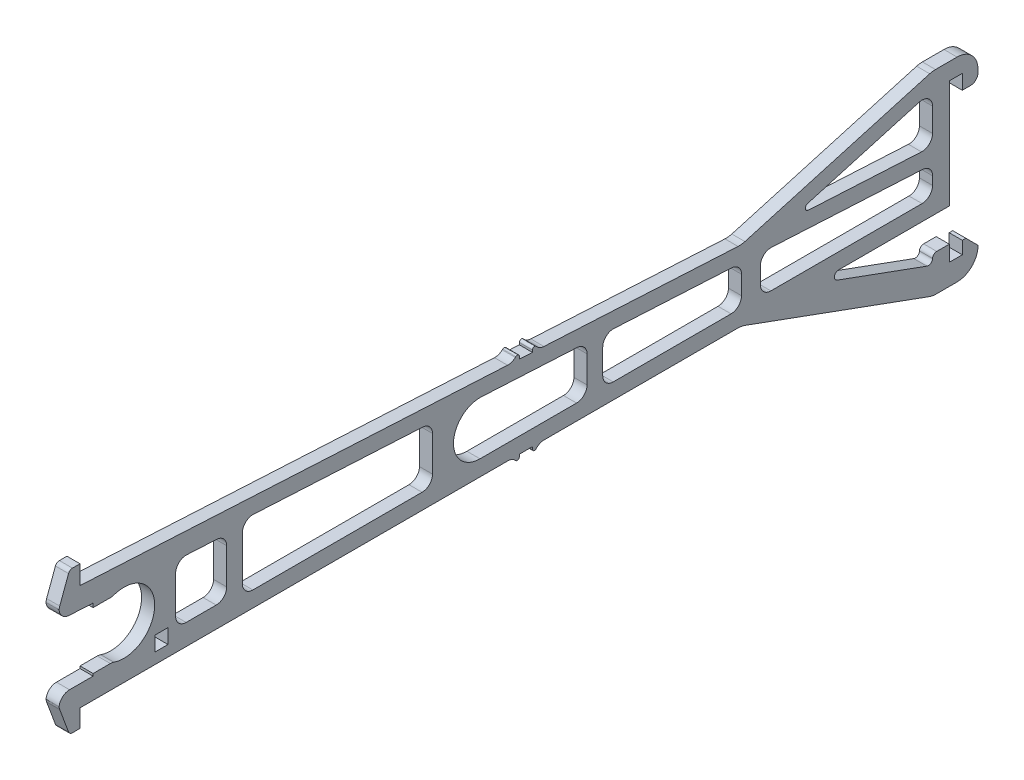
SolidWorks part; units mm, degrees
material "Delrin"
ref_plane "Front Plane" through (0, 0, 0) normal (0, 0, 1) x (1, 0, 0)
ref_plane "Top Plane" through (0, 0, 0) normal (0, 1, 0) x (1, 0, 0)
ref_plane "Right Plane" through (0, 0, 0) normal (1, 0, 0) x (0, 0, -1)
sketch "Sketch1" plane through (0, 0, 0) normal (1, 0, 0) x (0, 0, -1)
  line L0 (0.3361, 6.2648) -> (74.8851, 2.2655)
  line L1 (0, -6.2738) -> (74.8851, -6.2738)
  line L2 (98.044, 8.8972) -> (101.0158, 8.8972)
  line L3 (12.4587, 3.0708) -> (0.2, 3.7284)
  line L4 (12.4587, -3.7338) -> (0, -3.7338)
  line L5 (-5.3213, -3.7338) -> (-7.8613, -3.7338)
  line L6 (52.6413, 3.4588) -> (52.6413, 1.5538) construction
  line L7 (98.044, -6.2738) -> (98.044, 8.8972) construction
  line L8 (-5.3213, 0.003) -> (-5.3213, 22.0412) construction
  line L9 (0.3361, 6.2648) -> (-5.3213, 6.5683)
  line L10 (-5.3213, 6.5683) -> (-5.3213, 8.8599)
  line L11 (-5.3213, 8.8599) -> (-7.8613, 8.8599)
  line L12 (-7.8613, 8.8599) -> (-7.8613, 4.1609)
  line L13 (14.3637, 3.6073) -> (14.3637, 5.5123) construction
  line L14 (0, -6.2738) -> (-5.3213, -6.2738)
  line L15 (-5.3213, -6.2738) -> (-5.3213, -8.4328)
  line L16 (14.3637, 3.6073) -> (14.3637, -4.3688)
  line L17 (39.3251, 2.2682) -> (39.3251, -4.3688)
  line L18 (37.4201, 2.3704) -> (37.4201, -4.3688)
  line L19 (-5.3213, -8.4328) -> (-7.8613, -8.4328)
  line L20 (-7.8613, -8.4328) -> (-7.8613, -3.7338)
  line L21 (52.6413, -4.3688) -> (52.6413, -6.2738) construction
  line L22 (12.4587, 3.0708) -> (12.4587, -3.7338)
  line L23 (0, 3.7338) -> (0, -3.7338)
  line L24 (102.6668, 5.0872) -> (101.6508, 5.0872)
  line L25 (101.6508, 5.0872) -> (101.6508, 6.8652)
  line L26 (101.6508, 6.8652) -> (100.076, 6.8652)
  line L27 (100.076, 6.8652) -> (100.076, -6.2738)
  line L28 (100.076, -12.1848) -> (101.6508, -12.1848)
  line L29 (101.6508, -12.1848) -> (101.6508, -10.6608)
  line L30 (101.6508, -10.6608) -> (102.0826, -10.6608)
  line L31 (103.5558, -12.134) -> (103.5558, -12.1848)
  line L32 (101.0158, -14.7248) -> (98.044, -14.7248)
  line L33 (98.044, -14.7248) -> (98.044, -6.2738) construction
  line L34 (103.5558, 5.9762) -> (103.5558, 6.3572)
  line L35 (102.0826, -10.6608) -> (103.5558, -12.134)
  line L36 (77.1711, 0.2379) -> (77.1711, -4.3688)
  line L37 (74.8851, 0.3605) -> (74.8851, -4.3688)
  line L38 (74.8851, 2.2655) -> (98.044, 8.8972)
  line L39 (80.7132, 1.9529) -> (98.044, 6.9156)
  line L40 (74.8851, -6.2738) -> (98.044, -14.7248)
  line L41 (83.7765, -6.2738) -> (98.044, -11.4802)
  line L42 (75.93, -3.4105) -> (99.0889, -11.8615) construction
  line L43 (75.4095, 0.4341) -> (98.5684, 7.0658) construction
  line L44 (83.7765, -6.2738) -> (98.044, -6.2738)
  line L45 (-1.4111, 3.4569) -> (-3.7338, 3.4569)
  line L46 (80.7132, 1.9529) -> (98.044, 1.0232)
  line L47 (74.8851, -4.3678) -> (74.8851, 49995.6322) construction
  line L48 (98.044, 6.9156) -> (98.044, 1.0232)
  line L49 (98.044, -0.8818) -> (98.044, -4.3688)
  line L50 (100.076, -12.1848) -> (100.076, -10.2798)
  line L51 (98.044, -6.2738) -> (100.076, -6.2738)
  line L52 (100.076, -10.2798) -> (98.044, -10.2798)
  line L53 (98.044, -10.2798) -> (98.044, -11.4802)
  line L54 (14.3637, 3.6073) -> (37.4201, 2.3704)
  line L55 (14.3637, -4.3688) -> (37.4201, -4.3688)
  line L56 (39.3251, -4.3688) -> (74.8851, -4.3688)
  line L57 (39.3251, 2.2682) -> (74.8851, 0.3605)
  line L58 (77.1711, 0.2379) -> (98.044, -0.8818)
  line L59 (77.1711, -4.3688) -> (98.044, -4.3688)
  line L60 (-3.7338, 0) -> (-3.7338, 18.3871) construction
  line L61 (-3.7338, 3.9395) -> (-7.8613, 4.1609)
  line L62 (-3.7338, -3.7338) -> (-5.3213, -3.7338)
  line L63 (-3.7338, 3.4569) -> (-3.7338, 3.9395)
  line L64 (-1.4111, -3.4569) -> (-3.7338, -3.4569)
  line L65 (-3.7338, -3.4569) -> (-3.7338, -3.7338)
  line L66 (6.2738, 3.4026) -> (6.2738, -3.7338)
  line L67 (3.7338, 0) -> (3.7338, 11.926) construction
  line L68 (58.0576, 1.2633) -> (58.0576, -4.3688)
  line L69 (56.1526, 1.3655) -> (56.1526, -4.3688)
  line L70 (57.1051, -4.3688) -> (57.1051, 1.3144) construction
  line L71 (57.1051, -0.6088) -> (56.1526, -0.6088) construction
  line L72 (57.1051, -0.6088) -> (58.0576, -0.6088) construction
  arc A0 (0, -3.7338) -> (0, 3.7338) centre (0, 0) ccw
  circle A1 centre (0, 0) radius 6.2738 construction
  arc A2 (101.0158, 8.8972) -> (103.5558, 6.3572) centre (101.0158, 6.3572) cw
  arc A3 (103.5558, -12.1848) -> (101.0158, -14.7248) centre (101.0158, -12.1848) cw
  arc A4 (103.5558, 5.9762) -> (102.6668, 5.0872) centre (102.6668, 5.9762) cw
  arc A5 (0, 3.7338) -> (-1.4111, 3.4569) centre (0, 0) ccw
  circle A6 centre (0, 0) radius 3.7338 construction
  arc A7 (-1.4111, -3.4569) -> (0, -3.7338) centre (0, 0) ccw
  point P47 (103.5558, 8.8972)
  point P50 (103.5558, -14.7248)
  point P53 (103.5558, 5.0872)
  point P54 (103.5558, -10.6608)
  point P56 (103.5558, -10.6608)
  point P79 (3.5707, 1.0917)
  dimension "D1" = 7.4676
  dimension "D2" = 2.54
  dimension "D3" = 5.842
  dimension "D8" = 1.5748
  dimension "D18" = 2.54
  dimension "D19" = 2.54
  dimension "D20" = 0.889
  dimension "D21" = 35.56
  dimension "D5" = 37.4201
  dimension "D10" = 1.905
  dimension "D11" = 1.778
  dimension "D12" = 1.905
  dimension "D4" = 5.3842
  dimension "D9" = 1.5748
  dimension "D14" = 1.524
  dimension "D15" = 3.81
  dimension "D16" = 4.064
  dimension "D17" = 1.905
  dimension "D22" = 19.05
  dimension "D23" = 20.8729
  dimension "D24" = 2.032
  dimension "D25" = 2.286
  dimension "D29" = 1.905
  dimension "D13" = 2.54
  dimension "D30" = 4.699
  dimension "D31" = 1.905
  dimension "D32" = 17.78
  dimension "D33" = 1.5875
  dimension "D6" = 1.905
  dimension "D7" = 0.4826
  dimension "D34" = 2.54
  dimension "D35" = 1.905
  dimension "D27" = 3.048
  dimension "D28" = 1.905
extrude "Boss-Extrude1" add sketch "Sketch1" along normal blind 1.5875 contours A1 A0 | A4 L34 A2 L2 L38 L0 L9 L10 L11 L12 L49 L20 L19 L15 L14 L1 L40 L32 A3 L31 L35 L30 L29 L28 L50 L52 L53 L41 L44 L51 L27 L26 L25 L24 | L18 L17 | L22 L16 | L37 L36 | L57 L69 L56 L68 region at (0, 3.1279, -37.5496) region at (0, -0.1548, -4.5114) region at (0, -1.5271, -57.1022)
sketch "Sketch7" plane through (0, 0, 0) normal (-1, 0, 0) x (0, 0, 1)
  line L0 (6.5913, 8.8599) -> (7.8613, 5.4309)
  line L1 (5.3213, 8.8599) -> (7.8613, 8.8599) construction
  line L2 (7.8613, 8.8599) -> (7.8613, 4.1609) construction
  line L3 (6.5913, 8.8599) -> (7.8613, 8.8599)
  line L4 (7.8613, 8.8599) -> (7.8613, 5.4309)
  line L5 (6.5913, -8.4328) -> (7.8613, -5.0038)
  line L6 (5.3213, -8.4328) -> (7.8613, -8.4328) construction
  line L7 (7.8613, -8.4328) -> (7.8613, -3.7338) construction
  line L8 (6.5913, -8.4328) -> (7.8613, -8.4328)
  line L9 (7.8613, -8.4328) -> (7.8613, -5.0038)
  dimension "D1" = 1.27
  dimension "D2" = 1.27
  dimension "D3" = 1.27
extrude "Cut-Extrude2" cut sketch "Sketch7" against normal through all
fillet "Fillet1" radius 2.54 4 edges at (0.7937, 2.2655, -74.8851) (0.7937, 8.8972, -98.044) (0.7937, -6.2738, -74.8851) (0.7937, -14.7248, -98.044)
fillet "Fillet2" radius 1.27 20 edges at (0.7937, 1.0232, -98.044) (0.7937, 6.9156, -98.044) (0.7937, -4.3688, -14.3637) (0.7937, 3.6073, -14.3637) (0.7937, 2.3704, -37.4201) (0.7937, -4.3688, -37.4201) (0.7937, -4.3688, -77.1711) (0.7937, 0.2379, -77.1711) (0.7937, -4.3688, -98.044) (0.7937, -0.8818, -98.044) (0.7937, -4.3688, -74.8851) (0.7937, 0.3605, -74.8851) (0.7937, -3.7338, -6.2738) (0.7937, 3.4026, -6.2738) (0.7937, -3.7338, -12.4587) (0.7937, 3.0708, -12.4587) (0.7937, 1.3655, -56.1526) (0.7937, -4.3688, -56.1526) (0.7937, -4.3688, -58.0576) (0.7937, 1.2633, -58.0576)
fillet "Fillet3" radius 0.508 2 edges at (0.7937, -6.2738, -83.7765) (0.7937, -11.4802, -98.044)
fillet "Fillet4" radius 0.508 1 edges at (0.7937, -10.2798, -98.044)
sketch "Sketch4" plane through (1.5875, 0, 0) normal (1, 0, 0) x (0, 0, -1)
  line L0 (39.3251, 2.2682) -> (54.9506, 1.4299) construction
  line L1 (39.3251, -4.3688) -> (54.8826, -4.3688) construction
  line L2 (39.9601, -1.1558) -> (39.3251, -1.1558) construction
  line L6 (39.3251, 2.2682) -> (39.3251, -4.3688) construction
  line L7 (39.3251, 2.2682) -> (43.3452, 2.0525)
  line L8 (39.3251, 2.2682) -> (39.3251, -4.3688)
  line L9 (39.3251, -4.3688) -> (43.1731, -4.3688)
  arc A0 (43.3452, 2.0525) -> (43.1731, -4.3688) centre (43.1731, -1.1558) ccw
  dimension "D1" = 0.635
sketch "Sketch6" plane through (1.5875, 0, 0) normal (-1, 0, 0) x (0, 0, 1)
  line L0 (-47.0577, -6.2738) -> (-47.9467, -7.1628)
  line L1 (5.3213, 6.5683) -> (-74.4595, 2.2884) construction
  line L2 (-47.9467, -17.1193) -> (-47.9467, 10.2613) construction
  line L3 (-47.9467, -7.1628) -> (-47.9467, -6.2738)
  line L4 (-47.9467, -6.2738) -> (-47.0577, -6.2738)
  line L5 (-74.4361, -6.2738) -> (5.3213, -6.2738) construction
  line L6 (-48.7404, -10.0838) -> (-48.7404, 6.4573) construction
  line L7 (-49.5342, -10.0838) -> (-47.9467, -10.0838) construction
  line L8 (-49.5342, -6.2738) -> (-50.4232, -6.2738)
  line L9 (-49.5342, -7.1628) -> (-49.5342, -6.2738)
  line L10 (-50.4232, -6.2738) -> (-49.5342, -7.1628)
  line L11 (-50.4219, 3.5779) -> (-49.5342, 4.5145)
  line L13 (-49.5342, -17.1193) -> (-49.5342, 10.2613) construction
  line L14 (-49.5342, 4.5145) -> (-49.5342, 3.6255)
  line L15 (-49.5342, 3.6255) -> (-50.4219, 3.5779)
  line L16 (-47.9467, 3.7107) -> (-47.059, 3.7583)
  line L17 (-47.059, 3.7583) -> (-47.9467, 4.5997)
  line L18 (-47.9467, 4.5997) -> (-47.9467, 3.7107)
  dimension "D1" = 0.889
extrude "Boss-Extrude3" add sketch "Sketch6" along normal up to surface (1.5875 mm away) contours L4 L3 L0 | L8 L10 L9 | L15 L14 L11 | L17 L18 L16 | L18 L17 L16 | L14 L15 L11 | L10 L8 L9 | L3 L4 L0 region at (1.5875, -6.5701, -47.6504) region at (1.5875, -6.5701, -49.8305) region at (1.5875, 3.906, -49.8301) region at (1.5875, 4.0229, -47.6508) up to face at (0, -1.7797, -66.4859)
fillet "Fillet5" radius 1.27 4 edges at (0.7937, 3.5779, -50.4219) (0.7937, 3.7583, -47.059) (0.7937, -6.2738, -50.4232) (0.7937, -6.2738, -47.0577)
fillet "Fillet6" radius 0.254 4 edges at (0.7937, -7.1628, -49.5342) (0.7937, -7.1628, -47.9467) (0.7937, 4.5997, -47.9467) (0.7937, 4.5145, -49.5342)
extrude "Boss-Extrude4" add sketch "Sketch4" against normal up to surface (1.5875 mm away) up to face at (0, -1.7797, -66.4859)
sketch "Sketch5" plane through (1.5875, 0, 0) normal (1, 0, 0) x (0, 0, -1)
  line L8 (3.7592, -4.445) -> (3.7592, -4.953) construction
  line L9 (3.7592, -4.953) -> (5.3467, -4.953) construction
  line L10 (5.3467, -4.953) -> (5.3467, -4.445) construction
  line L11 (5.3467, -4.445) -> (5.3467, -3.683) construction
  line L12 (5.3467, -3.683) -> (5.3467, -3.175) construction
  line L13 (5.3467, -3.175) -> (3.7592, -3.175) construction
  line L14 (3.7592, -3.175) -> (3.7592, -3.683) construction
  line L15 (3.7592, -4.445) -> (3.7592, -3.683) construction
  line L16 (3.7592, -4.445) -> (3.7592, -4.953)
  line L17 (3.7592, -4.953) -> (5.3467, -4.953)
  line L18 (5.3467, -4.953) -> (5.3467, -4.445)
  line L19 (5.3467, -4.445) -> (5.3467, -3.683)
  line L20 (5.3467, -3.683) -> (5.3467, -3.175)
  line L21 (5.3467, -3.175) -> (3.7592, -3.175)
  line L22 (3.7592, -3.175) -> (3.7592, -3.683)
  line L23 (3.7592, -4.445) -> (3.7592, -3.683)
extrude "Cut-Extrude1" cut sketch "Sketch5" against normal up to next
fillet "Fillet9" radius 1.27 2 edges at (0.7937, -3.4569, 1.4111) (0.7937, 3.4569, 1.4111)
fillet "Fillet10" radius 0.381 1 edges at (0.7937, 1.9529, -80.7132)
fillet "Fillet12" radius 1.27 4 edges at (0.7937, -5.0038, 7.8613) (0.7937, -3.7338, 7.8613) (0.7937, 5.4309, 7.8613) (0.7937, 4.1609, 7.8613)
fillet "Fillet13" radius 0.508 2 edges at (0.7937, 8.8599, 6.5913) (0.7937, -8.4328, 6.5913)
